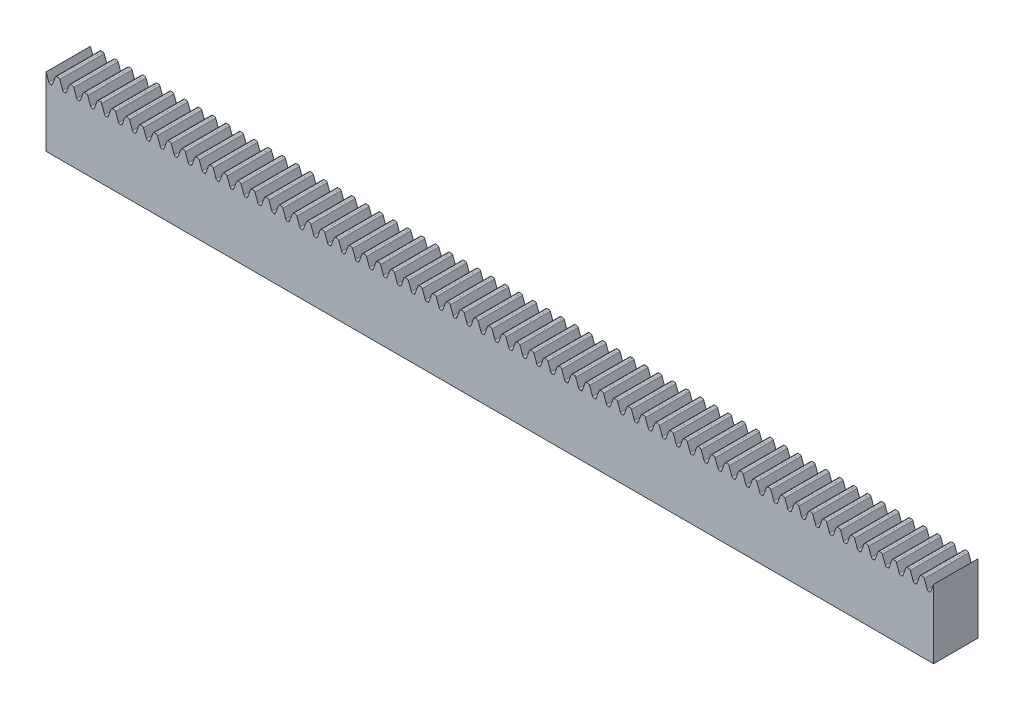
SolidWorks part; units mm, degrees
ref_plane "Front Plane" through (0, 0, 0) normal (0, 0, 1) x (1, 0, 0)
ref_plane "Top Plane" through (0, 0, 0) normal (0, 1, 0) x (1, 0, 0)
ref_plane "Right Plane" through (0, 0, 0) normal (1, 0, 0) x (0, 0, -1)
sketch "Sketch1" plane through (0, 0, 0) normal (0, 0, 1) x (1, 0, 0)
  line L0 (-50, 6) -> (-50, -6) construction
  line L1 (-50, -6) -> (50, -6) construction
  line L2 (50, -6) -> (50, 6) construction
  line L4 (0, 6) -> (0, -6) construction
  line L5 (-50, 5.5) -> (50, 5.5) construction
  line L6 (-48.9054, 6) -> (-48.484, 6) construction
  line L7 (-48.484, 6) -> (-48.0745, 4.875) construction
  line L8 (-48.9054, 6) -> (-49.3149, 4.875) construction
  line L9 (-49.3149, 4.875) -> (-48.0745, 4.875) construction
  line L10 (-48.6947, 6) -> (-48.6947, 4.875) construction
  line L11 (-50, 0) -> (-45.5531, 0) construction
  line L12 (50, 0) -> (45.5531, 0) construction
  point P15 (-47.1239, 6)
  point P16 (-31.5, -6)
  point P17 (-48.302, 5.5)
  point P18 (-49.0874, 5.5)
  point P21 (-0.25, -6)
  dimension "Length" = 100
  dimension "Height" = 12
  dimension "Approximate Number of Teeth" = 63
  dimension "Pressure Angle" = 20
  dimension "Circular Pitch" = 1.5708
  dimension "Addendum" = 0.5
  dimension "Dedendum" = 0.625
  dimension "Circular Tooth Thickness" = 0.7854
  dimension "Module" = 0.5
  dimension "Rack Length" = 97.3894
  dimension "D1" = 3.1416
sketch "Sketch2" plane through (0, 0, 0) normal (1, 0, 0) x (0, 0, -1)
  line L0 (-2.5, 0) -> (2.5, 0) construction
  dimension "Face Width" = 5
sketch "Sketch3" plane through (0, 0, 0) normal (0, 0, 1) x (1, 0, 0)
  line L1 (-50, 6) -> (50, 6)
  line L2 (-50, 6) -> (-50, -6)
  line L3 (-50, -6) -> (50, -6)
  line L4 (50, 6) -> (50, -6)
extrude "Boss-Extrude1" add sketch "Sketch3" against normal up to vertex (2.5 mm away) and the other way up to vertex (2.5 mm away) up to point (0, 0, -2.5) other way up to point (0, 0, 2.5)
sketch "Sketch4" plane through (0, 0, 0) normal (0, 0, 1) x (1, 0, 0)
  line L0 (-48.6947, 6) -> (-47.1239, 6) construction
  line L9 (-47.9093, 6) -> (-47.9093, 4.875)
  line L10 (-47.9093, 4.875) -> (-48.0745, 4.875)
  line L11 (-48.0745, 4.875) -> (-48.484, 6)
  line L12 (-48.484, 6) -> (-47.9093, 6)
  line L13 (-48.9054, 6) -> (-49.3149, 4.875)
  line L14 (-49.3149, 4.875) -> (-49.4801, 4.875)
  line L15 (-49.4801, 4.875) -> (-49.4801, 6)
  line L16 (-49.4801, 6) -> (-48.9054, 6)
  line L17 (50, 6) -> (-50, 6) construction
  line L18 (-48.9054, 6) -> (-48.7879, 6)
  line L19 (-48.6014, 6) -> (-48.484, 6)
  arc A0 (-49.4323, 4.875) -> (-49.2747, 4.9854) centre (-49.4323, 5.0428) ccw
  arc A1 (-48.1147, 4.9854) -> (-47.957, 4.875) centre (-47.957, 5.0428) ccw
  arc A2 (-48.9456, 5.8896) -> (-48.7879, 6) centre (-48.7879, 5.8322) cw
  arc A3 (-48.6014, 6) -> (-48.4438, 5.8896) centre (-48.6014, 5.8322) cw
  dimension "D1" = 0.1678
extrude "Cut-Extrude1" cut sketch "Sketch4" against normal through all both and the other way through all contours L14 A0 L13 L16 L15 | L13 A2 L18 | L19 A3 L11 | L11 A1 L10 L9 L12 region at (-48.1135, 5.5452, 0) region at (-48.5005, 5.9764, 0) region at (-48.8889, 5.9764, 0) region at (-49.2759, 5.5452, 0)
pattern_linear "LPattern1" count 64 spacing 1.5708 along (1, 0, 0) count 2 spacing 1.5708 along (-1, 0, 0) of "Cut-Extrude1"
sketch "Drawing Refernce 1" plane through (0, 0, 2.5) normal (0, 0, 1) x (1, 0, 0)
  line L0 (-50, 0) -> (50, 0) construction
  point P6 (-35, 0)
  point P7 (-27.5, 0)
  point P8 (35, 0)
  dimension "D1" = 15
  dimension "D2" = 22.5
  dimension "D3" = 15
sketch "Sketch5" plane through (0, 0, 2.5) normal (0, 0, 1) x (1, 0, 0)
  line L0 (50, -6) -> (50, 5.8495) construction
  line L1 (-50, -6) -> (50, -6)
  line L2 (-50, -6) -> (-50, -1.9)
  line L3 (-50, -1.9) -> (50, -1.9)
  line L4 (50, -6) -> (50, -1.9)
  dimension "D1" = 4.1
extrude "Cut-Extrude2" cut sketch "Sketch5" against normal through all
equation "\"Diametral Pitch\"= 1 / \"Module\""
equation "\"Pressure Angle\"=20"
equation "\"Dedendum\"= 1.25 / \"Diametral Pitch\""
equation "\"Addendum\"= 1 / \"Diametral Pitch\""
equation "\"WorkingDepth\"= 2 / \"Diametral Pitch\""
equation "\"WholeDepth\"= 2.25 / \"Diametral Pitch\""
equation "\"Clearance\"= 0.25 / \"Diametral Pitch\""
equation "\"ToothThickness\"= ( pi / 2 ) / \"Diametral Pitch\""
equation "\"CircularPitch\"= pi / \"Diametral Pitch\""
equation "\"Fillet\"= \"Clearance\" * cos ( \"Pressure Angle\" ) * tan ( ( 90 + \"Pressure Angle\" ) / 2 )"
equation "\"Module\"= 0.5"
equation "\"Addendum@Sketch1\"=\"Addendum\""
equation "\"Pressure Angle@Sketch1\"=\"Pressure Angle\""
equation "\"Dedendum@Sketch1\"=\"Dedendum\""
equation "\"Circular Pitch@Sketch1\"=\"CircularPitch\""
equation "\"Circular Tooth Thickness@Sketch1\"=\"ToothThickness\""
equation "\"Module@Sketch1\"=\"Module\""
equation "\"Approximate Number of Teeth@Sketch1\" = int ( \"Length@Sketch1\" /  ( 2 * \"Circular Tooth Thickness@Sketch1\" )  ) "
equation "\"Rack Length@Sketch1\" = \"Circular Pitch@Sketch1\" *  ( \"Approximate Number of Teeth@Sketch1\" - 1 ) "
equation "\"D3@LPattern1\"=\"CircularPitch\""
equation "\"D1@LPattern1\"=\"Approximate Number of Teeth@Sketch1\"+1"
equation "\"D1@Sketch1\"=\"Circular Pitch@Sketch1\"*2"
equation "\"D1@Sketch4\"=\"Fillet\""
equation "\"D4@LPattern1\"=\"CircularPitch\""
equation "\"D2@Drawing Refernce 1\"=\"D1@Drawing Refernce 1\"*1.5"
equation "\"D3@Drawing Refernce 1\"=\"D1@Drawing Refernce 1\""
